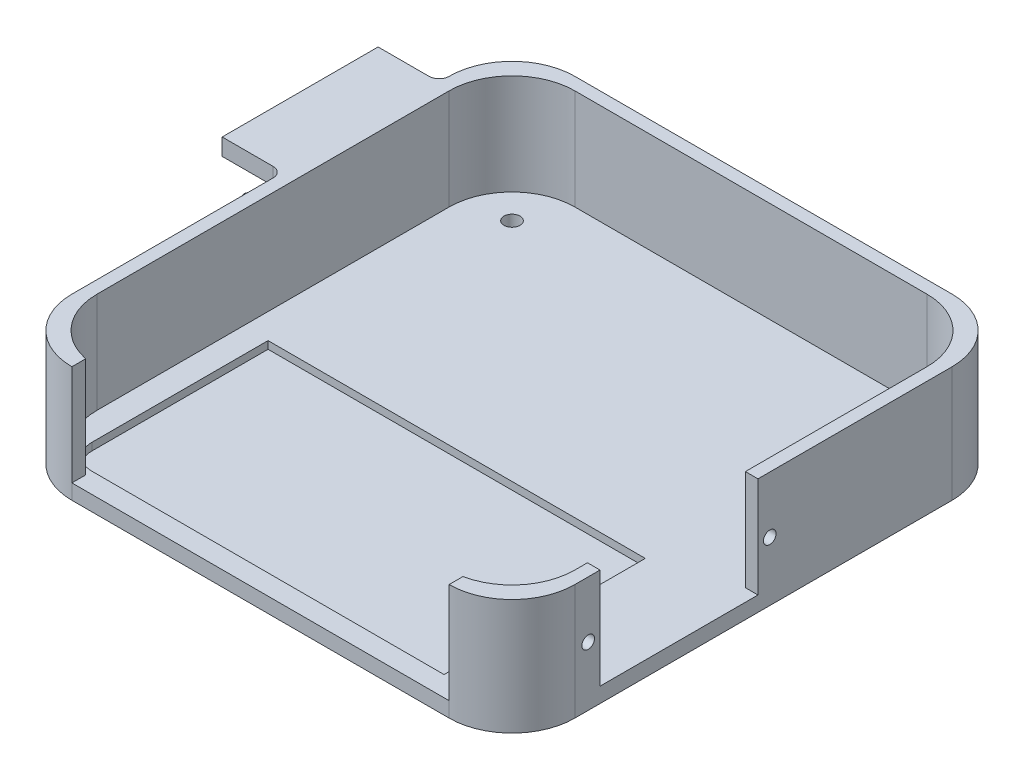
SolidWorks part; units mm, degrees
note: The reader was unsure of these and kept them because the rebuilt part matched: shared geometry of "Sketch1<2>".
ref_plane "Front Plane" through (0, 0, 0) normal (0, 0, 1) x (1, 0, 0)
ref_plane "Top Plane" through (0, 0, 0) normal (0, 1, 0) x (1, 0, 0)
ref_plane "Right Plane" through (0, 0, 0) normal (1, 0, 0) x (0, 0, -1)
sketch "Sketch1" plane through (0, 0, 0) normal (0, 1, 0) x (1, 0, 0)
  line L1 (12.5, 0) -> (87.5, 0)
  line L2 (0, 12.5) -> (0, 87.5)
  line L3 (12.5, 100) -> (87.5, 100)
  line L4 (100, 12.5) -> (100, 87.5)
  line L5 (15, 97.5) -> (85, 97.5)
  line L6 (2.5, 85) -> (2.5, 15)
  line L7 (15, 2.5) -> (85, 2.5)
  line L8 (97.5, 85) -> (97.5, 15)
  arc A0 (87.5, 0) -> (100, 12.5) centre (87.5, 12.5) ccw
  arc A1 (87.5, 100) -> (100, 87.5) centre (87.5, 87.5) cw
  arc A2 (0, 87.5) -> (12.5, 100) centre (12.5, 87.5) cw
  arc A3 (12.5, 0) -> (0, 12.5) centre (12.5, 12.5) cw
  arc A4 (85, 2.5) -> (97.5, 15) centre (85, 15) ccw
  arc A5 (2.5, 15) -> (15, 2.5) centre (15, 15) ccw
  arc A6 (97.5, 85) -> (85, 97.5) centre (85, 85) ccw
  arc A7 (15, 97.5) -> (2.5, 85) centre (15, 85) ccw
  point P11 (100, 0)
  point P16 (0, 100)
  point P19 (0, 0)
  point P22 (97.5, 2.5)
  point P25 (2.5, 2.5)
  point P30 (2.5, 97.5)
  dimension "D7" = 12.5
  dimension "D1" = 100
  dimension "D2" = 100
  dimension "D3" = 95
  dimension "D4" = 95
  dimension "D5" = 2.5
  dimension "D6" = 2.5
extrude "Boss-Extrude1" add sketch "Sketch1" along normal blind 23
extrude "Boss-Extrude2" add sketch "Sketch1<2>" along normal blind 3 contours L5 A7 L6 A5 L7 A4 L8 A6
sketch "Sketch1<2>" plane through (0, 0, 0) normal (0, 1, 0) x (1, 0, 0) same geometry as "Sketch1"
sketch "Sketch4" plane through (0, 3, 0) normal (0, 1, 0) x (1, 0, 0)
  line L0 (6.1612, 93.8388) -> (93.8388, 6.1612) construction
  line L1 (93.8388, 93.8388) -> (6.1612, 6.1612) construction
  arc A0 (15, 97.5) -> (2.5, 85) centre (15, 85) ccw construction
  arc A1 (85, 2.5) -> (97.5, 15) centre (85, 15) ccw construction
  arc A2 (97.5, 85) -> (85, 97.5) centre (85, 85) ccw construction
  arc A3 (2.5, 15) -> (15, 2.5) centre (15, 15) ccw construction
  circle A4 centre (88.8909, 11.1091) radius 1.6
  circle A5 centre (11.1091, 88.8909) radius 1.6
  point P21 (50, 50)
  dimension "D2" = 3.2
  dimension "D1" = 55
extrude "Cut-Extrude1" cut sketch "Sketch4" against normal through all both and the other way through all
sketch "Sketch5" plane through (0, 3, 0) normal (0, 1, 0) x (1, 0, 0)
  line L0 (97.5, 85) -> (97.5, 15) construction
  line L1 (82.5, 4) -> (12.5, 4)
  line L2 (82.5, 4) -> (82.5, 44)
  line L3 (82.5, 44) -> (7.5, 44)
  line L4 (7.5, 9) -> (7.5, 44)
  line L5 (15, 2.5) -> (85, 2.5) construction
  line L6 (2.5, 85) -> (2.5, 15) construction
  arc A0 (7.5, 9) -> (12.5, 4) centre (12.5, 9) ccw
  dimension "D5" = 5
  dimension "D1" = 15
  dimension "D2" = 1.5
  dimension "D3" = 5
  dimension "D4" = 40
extrude "Cut-Extrude2" cut sketch "Sketch5" against normal blind 1.5
sketch "Sketch6" plane through (0, 0, 0) normal (0, 0, 1) x (1, 0, 0)
  line L0 (87.5, 23) -> (87.5, 0) construction
  line L1 (12.5, 23) -> (87.5, 23)
  line L2 (12.5, 23) -> (12.5, 3)
  line L3 (12.5, 3) -> (87.5, 3)
  line L4 (87.5, 23) -> (87.5, 3)
  line L5 (12.5, 0) -> (87.5, 0) construction
  dimension "D1" = 3
extrude "Cut-Extrude4" cut sketch "Sketch6" against normal blind 5
sketch "Sketch8" plane through (100, 0, 0) normal (1, 0, 0) x (0, 0, -1)
  line L0 (12.5, 0) -> (87.5, 0) construction
  line L1 (17.5, 23) -> (48.9, 23)
  line L2 (17.5, 23) -> (17.5, 3)
  line L3 (17.5, 3) -> (48.9, 3)
  line L4 (48.9, 23) -> (48.9, 3)
  line L5 (33.2, 23) -> (33.2, 3) construction
  line L6 (12.5, 23) -> (12.5, 0) construction
  circle A0 centre (15.15, 11.7633) radius 1.25
  circle A1 centre (51.25, 11.7633) radius 1.25
  dimension "D3" = 2.5
  dimension "D1" = 20
  dimension "D2" = 31.4
  dimension "D4" = 2.35
  dimension "D5" = 3
  dimension "D6" = 5
extrude "Cut-Extrude5" cut sketch "Sketch8" against normal blind 5
sketch "Sketch9" plane through (0, 0, 0) normal (-1, 0, 0) x (0, 0, 1)
  line L0 (-87.5, 23) -> (-87.5, 0) construction
  line L1 (-57.5, 13.75) -> (-55.5, 13.75)
  line L2 (-57.5, 13.75) -> (-57.5, 9.25)
  line L3 (-57.5, 9.25) -> (-55.5, 9.25)
  line L4 (-55.5, 13.75) -> (-55.5, 9.25)
  line L5 (-87.5, 0) -> (-12.5, 0) construction
  dimension "D1" = 4.5
  dimension "D2" = 2
  dimension "D3" = 30
  dimension "D4" = 9.25
extrude "Boss-Extrude3" add sketch "Sketch9" along normal blind 10
fillet "Fillet2" radius 1 8 edges at (0, 11.5, -57.5) (0, 11.5, -55.5) (-5, 13.75, -55.5) (-5, 13.75, -57.5) (-10, 11.5, -55.5) (-10, 11.5, -57.5) (-5, 9.25, -57.5) (-5, 9.25, -55.5)
sketch "Sketch10" plane through (0, 0, 0) normal (0, 1, 0) x (1, 0, 0)
  line L0 (0, 87.5) -> (0, 12.5) construction
  line L1 (0, 85.5) -> (-12.12, 85.5)
  line L2 (0, 85.5) -> (0, 54.5)
  line L3 (0, 54.5) -> (-12.12, 54.5)
  line L4 (-12.12, 85.5) -> (-12.12, 54.5)
  dimension "D1" = 31
  dimension "D2" = 12.12
  dimension "D3" = 0
  dimension "D4" = 42
extrude "Boss-Extrude4" add sketch "Sketch10" along normal blind 2.6
fillet "Fillet3" radius 2 1 edges at (0, 1.3, -54.5)
fillet "Fillet5" radius 2 2 edges at (0, 1.3, -85.5) (0, 0, -86.5)
sketch "Sketch11" plane through (0, 2.6, 0) normal (0, 1, 0) x (1, 0, 0)
  line L1 (-12.12, 85.5) -> (-10.12, 85.5)
  line L2 (-12.12, 85.5) -> (-12.12, 61.5)
  line L3 (-12.12, 61.5) -> (-10.12, 61.5)
  line L4 (-10.12, 85.5) -> (-10.12, 61.5)
  dimension "D1" = 24
  dimension "D2" = 2
extrude "Boss-Extrude5" add sketch "Sketch11" along normal blind 4
fillet "Fillet6" radius 1 1 edges at (-12.12, 6.6, -73.5)
fillet "Fillet7" radius 1 1 edges at (-10.12, 2.6, -73.5)
sketch "Sketch12" plane through (0, 2.6, 0) normal (0, 1, 0) x (1, 0, 0)
  line L1 (-12.12, 54.5) -> (-2, 54.5)
  line L2 (-12.12, 54.5) -> (-12.12, 56.5)
  line L3 (-12.12, 56.5) -> (-2, 56.5)
  line L4 (-2, 54.5) -> (-2, 56.5)
  dimension "D1" = 2
extrude "Boss-Extrude6" add sketch "Sketch12" along normal blind 0.75
ref_plane "Plane1" through (0, 11.5, 0) normal (0, 1, 0) x (1, 0, 0)
mirror "Mirror1" about plane through (0, 11.5, 0) normal (0, 1, 0) of "Fillet3", "Fillet5", "Boss-Extrude4", "Boss-Extrude6", "Fillet6", "Boss-Extrude5", "Fillet7"
